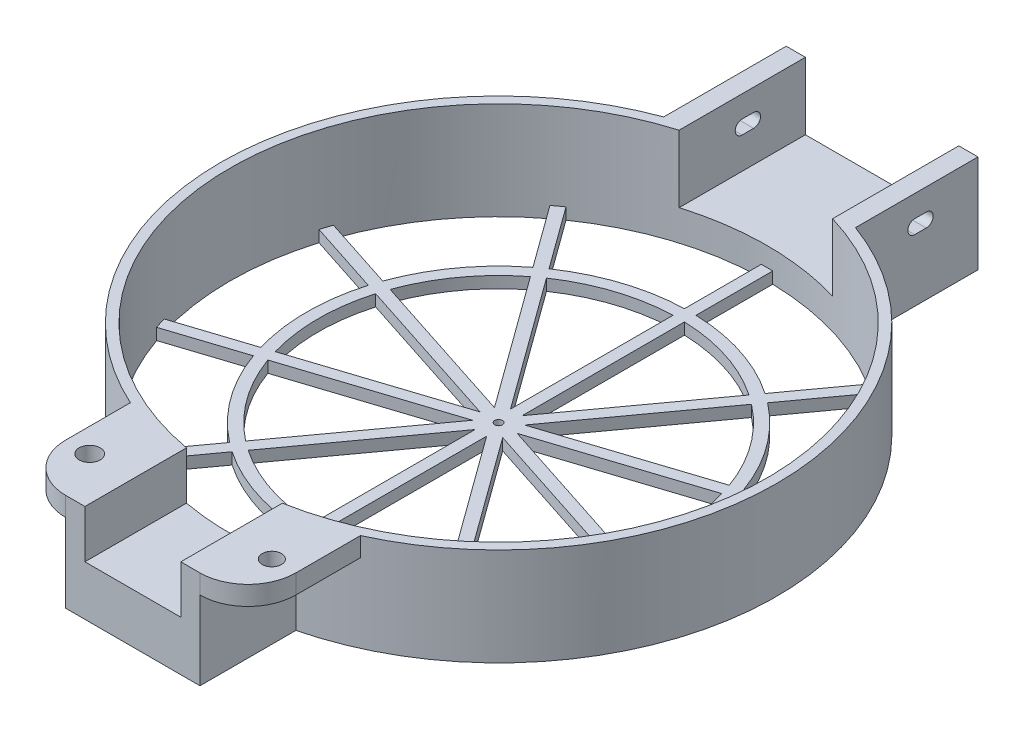
SolidWorks part; units mm, degrees
ref_plane "Front Plane" through (0, 0, 0) normal (0, 0, 1) x (1, 0, 0)
ref_plane "Top Plane" through (0, 0, 0) normal (0, 1, 0) x (1, 0, 0)
ref_plane "Right Plane" through (0, 0, 0) normal (1, 0, 0) x (0, 0, -1)
sketch "Sketch1" plane through (0, 0, 0) normal (0, 1, 0) x (1, 0, 0)
  line L0 (1.5, 69.9839) -> (0, 70.9924)
  line L2 (1.5, 69.9839) -> (1.5, 4.6165)
  line L4 (-1.5, 69.9839) -> (-1.5, 4.6165)
  line L5 (-0.8687, 69.9946) -> (-0.1565, 47.2626) construction
  line L7 (0, 70.9924) -> (-1.5, 69.9839)
  line L8 (41.7283, 57.4341) -> (39.922, 57.4999)
  line L9 (42.349, 55.7365) -> (41.7283, 57.4341)
  line L10 (42.349, 55.7365) -> (3.9271, 2.8532)
  line L11 (39.922, 57.4999) -> (1.5, 4.6165)
  line L12 (67.5178, 21.9379) -> (66.0951, 23.0528)
  line L13 (67.0222, 20.1996) -> (67.5178, 21.9379)
  line L14 (67.0222, 20.1996) -> (4.8541, 0)
  line L15 (66.0951, 23.0528) -> (3.9271, 2.8532)
  line L16 (67.5178, -21.9379) -> (67.0222, -20.1996)
  line L17 (66.0951, -23.0528) -> (67.5178, -21.9379)
  line L18 (66.0951, -23.0528) -> (3.9271, -2.8532)
  line L19 (67.0222, -20.1996) -> (4.8541, 0)
  line L20 (41.7283, -57.4341) -> (42.349, -55.7365)
  line L21 (39.922, -57.4999) -> (41.7283, -57.4341)
  line L22 (39.922, -57.4999) -> (1.5, -4.6165)
  line L23 (42.349, -55.7365) -> (3.9271, -2.8532)
  line L24 (0, -70.9924) -> (1.5, -69.9839)
  line L25 (-1.5, -69.9839) -> (0, -70.9924)
  line L26 (-1.5, -69.9839) -> (-1.5, -4.6165)
  line L27 (1.5, -69.9839) -> (1.5, -4.6165)
  line L28 (-41.7283, -57.4341) -> (-39.922, -57.4999)
  line L29 (-42.349, -55.7365) -> (-41.7283, -57.4341)
  line L30 (-42.349, -55.7365) -> (-3.9271, -2.8532)
  line L31 (-39.922, -57.4999) -> (-1.5, -4.6165)
  line L32 (-67.5178, -21.9379) -> (-66.0951, -23.0528)
  line L33 (-67.0222, -20.1996) -> (-67.5178, -21.9379)
  line L34 (-67.0222, -20.1996) -> (-4.8541, 0)
  line L35 (-66.0951, -23.0528) -> (-3.9271, -2.8532)
  line L36 (-67.5178, 21.9379) -> (-67.0222, 20.1996)
  line L37 (-66.0951, 23.0528) -> (-67.5178, 21.9379)
  line L38 (-66.0951, 23.0528) -> (-3.9271, 2.8532)
  line L39 (-67.0222, 20.1996) -> (-4.8541, 0)
  line L40 (-41.7283, 57.4341) -> (-42.349, 55.7365)
  line L41 (-39.922, 57.4999) -> (-41.7283, 57.4341)
  line L42 (-39.922, 57.4999) -> (-1.5, 4.6165)
  line L43 (-42.349, 55.7365) -> (-3.9271, 2.8532)
  line L60 (-0.1565, 47.2626) -> (0.8687, 69.9946) construction
  circle A0 centre (0, 0) radius 72.5
  circle A1 centre (0, 0) radius 70
  point P4 (0, 42.2662)
  point P59 (0, 0)
  dimension "D1" = 145
  dimension "D2" = 140
  dimension "D4" = 3
  dimension "D3" = 10
extrude "Boss-Extrude4" add sketch "Sketch1" along normal blind 16 contours A0 | A1
extrude "Boss-Extrude5" add sketch "Sketch1<11>" along normal blind 50 contours L26 L25 L24 L27 L22 L21 L20 L23 L18 L17 L16 L19 L14 L13 L12 L15 L10 L9 L8 L11 L2 L0 L7 L4 L42 L41 L40 L43 L38 L37 L36 L39 L34 L33 L32 L35 L30 L29 L28 L31
sketch "Sketch1<11>" plane through (0, 0, 0) normal (0, 1, 0) x (1, 0, 0) same geometry as "Sketch1"
sketch "Sketch2" plane through (0, 0, 0) normal (0, -1, 0) x (1, 0, 0)
  circle A0 centre (0, 0) radius 1
extrude "Cut-Extrude1" cut sketch "Sketch2" against normal through all
sketch "Sketch3" plane through (0, 0, 0) normal (0, -1, 0) x (1, 0, 0)
  circle A0 centre (0, 0) radius 47
  circle A1 centre (0, 0) radius 50
  circle A2 centre (0, 0) radius 70 construction
  dimension "D1" = 3
  dimension "D2" = 20
extrude "Boss-Extrude6" add sketch "Sketch3" against normal up to surface (50 mm away) contours A0 | A1 up to face at (0, 50, -1)
extrude "Boss-Extrude7" add sketch "Sketch1<12>" along normal blind 72.5 contours A1 | A0
sketch "Sketch1<12>" plane through (0, 0, 0) normal (0, 1, 0) x (1, 0, 0) same geometry as "Sketch1"
sketch "Sketch5" plane through (0, 0, 0) normal (0, 0, 1) x (1, 0, 0)
  line L0 (72.5, 72.5) -> (-72.5, 72.5) construction
  line L1 (-12.5, 85) -> (12.5, 85)
  line L2 (-12.5, 85) -> (-12.5, 60)
  line L3 (-12.5, 60) -> (12.5, 60)
  line L4 (12.5, 85) -> (12.5, 60)
  line L5 (-12.5, 85) -> (12.5, 60) construction
  line L6 (-12.5, 60) -> (12.5, 85) construction
  point P0 (0, 72.5)
  dimension "D1" = 25
  dimension "D2" = 25
sketch "Sketch6" plane through (0, 72.5, 0) normal (0, 1, 0) x (1, 0, 0)
  line L0 (-12.5, -1004.9467) -> (-12.5, -95.3562) construction
  line L1 (-12.5, -95.3562) -> (12.5, -95.3562)
  line L2 (12.5, -1000) -> (12.5, -95.3562) construction
  line L3 (12.5, -70.3562) -> (-12.5, -70.3562)
  line L4 (-12.5, -70.3562) -> (-12.5, 1004.2764) construction
  line L5 (12.5, -70.3562) -> (12.5, 49000) construction
  line L6 (12.5, -95.3562) -> (17.5, -95.3562)
  line L8 (12.5, -70.3562) -> (17.5, -70.3562)
  line L9 (17.5, -95.3562) -> (17.5, -70.3562)
  line L10 (-12.5, -95.3562) -> (-17.5, -95.3562)
  line L12 (-12.5, -70.3562) -> (-17.5, -70.3562)
  line L13 (-17.5, -95.3562) -> (-17.5, -70.3562)
  circle A0 centre (0, 0) radius 72.5 construction
  dimension "D1" = 5
  dimension "D2" = 5
  dimension "D3" = 25
  dimension "D4" = 25
  dimension "D5" = 12.5
extrude "Boss-Extrude8" add sketch "Sketch6" against normal blind 26
extrude "Cut-Extrude4" cut sketch "Sketch5" along normal blind 137.5
sketch "Sketch7" plane through (0, 72.5, 0) normal (0, 1, 0) x (1, 0, 0)
  line L1 (-17.5, -70.3562) -> (-17.5, -95.3562) construction
  line L2 (17.5, -95.3562) -> (17.5, -70.3562) construction
  line L6 (-30, -82.8562) -> (-30, -66.0019)
  line L7 (-30, -66.0019) -> (-17.5, -70.3562)
  line L8 (30, -82.8562) -> (30, -66.0019)
  line L9 (30, -66.0019) -> (17.5, -70.3562)
  line L10 (-17.5, -70.3562) -> (-17.5, -95.3562)
  line L11 (17.5, -70.3562) -> (17.5, -95.3562)
  line L13 (12.5, -95.3562) -> (-12.5, -95.3562) construction
  arc A0 (-30, -82.8562) -> (-17.5, -95.3562) centre (-17.5, -82.8562) ccw
  arc A1 (17.5, -95.3562) -> (30, -82.8562) centre (17.5, -82.8562) ccw
  circle A2 centre (0, 0) radius 72.5 construction
  circle A3 centre (-23.75, -82.8562) radius 2.75
  circle A4 centre (23.75, -82.8562) radius 2.5
  point P6 (0, -82.8562)
  dimension "D1" = 12.5
  dimension "D4" = 5.5
  dimension "D5" = 12.5
  dimension "D6" = 5
  dimension "D8" = 12.5
  dimension "D2" = 12.5
  dimension "D3" = 6.25
  dimension "D7" = 6.25
extrude "Boss-Extrude9" add sketch "Sketch7" against normal blind 5
sketch "Sketch12" plane through (0, 0, 0) normal (0, 0, 1) x (1, 0, 0)
  line L0 (72.5, 72.5) -> (-72.5, 72.5) construction
  line L1 (20, 95) -> (-20, 95)
  line L2 (20, 95) -> (20, 50)
  line L3 (20, 50) -> (-20, 50)
  line L4 (-20, 95) -> (-20, 50)
  line L5 (20, 95) -> (-20, 50) construction
  line L6 (20, 50) -> (-20, 95) construction
  point P0 (0, 72.5)
  dimension "D1" = 40
  dimension "D2" = 22.5
extrude "Cut-Extrude5" cut sketch "Sketch12" against normal blind 180
sketch "Sketch15" plane through (0, 72.5, 0) normal (0, 1, 0) x (1, 0, 0)
  line L0 (-20, 69.6868) -> (-20, 99.6868) construction
  line L1 (-25, 103.0533) -> (25, 103.0533)
  line L3 (20, 69.6868) -> (20, 99.6868) construction
  line L4 (25, 103.0533) -> (25, 68.0533)
  line L5 (-25, 103.0533) -> (-25, 68.0533)
  arc A0 (30, -66.0019) -> (20, 69.6868) centre (0, 0) ccw construction
  arc A1 (-20, 69.6868) -> (-30, -66.0019) centre (0, 0) ccw construction
  arc A2 (-25, 68.0533) -> (25, 68.0533) centre (0, 0) cw
  dimension "D1" = 30
  dimension "D2" = 5
  dimension "D3" = 5
  dimension "D4" = 35
  dimension "D5" = 35
extrude "Boss-Extrude11" add sketch "Sketch15" against normal blind 49.5969
extrude "Cut-Extrude6" cut sketch "Sketch12<2>" against normal blind 199.5
sketch "Sketch12<2>" plane through (0, 0, 0) normal (0, 0, 1) x (1, 0, 0) same geometry as "Sketch12"
sketch "Sketch17" plane through (0, 22.9031, 0) normal (0, -1, 0) x (1, 0, 0)
  line L3 (26.6747, -100.002) -> (-27.9148, -100.002)
  line L4 (26.6747, -100.002) -> (26.6747, -105.8478)
  line L5 (26.6747, -105.8478) -> (-27.9148, -105.8478)
  line L6 (-27.9148, -100.002) -> (-27.9148, -105.8478)
extrude "Cut-Extrude7" cut sketch "Sketch17" against normal through all both and the other way through all
sketch "Sketch20" plane through (25, 0, 0) normal (1, 0, 0) x (0, 0, -1)
  line L0 (83.502, 65) -> (86.502, 65) construction
  line L1 (83.502, 66.8) -> (86.502, 66.8)
  line L2 (83.502, 63.2) -> (86.502, 63.2)
  line L3 (100.002, 50) -> (67.082, 50) construction
  line L4 (100.002, 72.5) -> (100.002, 22.9031) construction
  arc A0 (83.502, 66.8) -> (83.502, 63.2) centre (83.502, 65) ccw
  arc A1 (86.502, 63.2) -> (86.502, 66.8) centre (86.502, 65) ccw
  point P2 (85.002, 65)
  dimension "D1" = 1.8
  dimension "D2" = 3
  dimension "D3" = 15
  dimension "D4" = 15
extrude "Cut-Extrude8" cut sketch "Sketch20" against normal through all both and the other way through all
sketch "Sketch22" plane through (0, 22.9031, 0) normal (0, -1, 0) x (1, 0, 0)
  line L1 (-5, -82.3274) -> (5, -82.3274)
  line L2 (-5, -82.3274) -> (-5, -72.3274)
  line L3 (-5, -72.3274) -> (5, -72.3274)
  line L4 (5, -82.3274) -> (5, -72.3274)
  line L5 (-5, -82.3274) -> (5, -72.3274) construction
  line L6 (-5, -72.3274) -> (5, -82.3274) construction
  circle A0 centre (0, 0) radius 72.5 construction
  point P0 (0, -77.3274)
  dimension "D1" = 10
  dimension "D2" = 10
extrude "Boss-Extrude12" add sketch "Sketch22" along normal up to surface (22.9031 mm away) up to face at (-47.5332, 0, 34.5349)
sketch "Sketch24" plane through (1.5, 0, 0) normal (1, 0, 0) x (0, 0, -1)
  line L1 (-93.1955, 47) -> (122.6721, 47)
  line L2 (-93.1955, 47) -> (-93.1955, -14.868)
  line L3 (-93.1955, -14.868) -> (122.6721, -14.868)
  line L4 (122.6721, 47) -> (122.6721, -14.868)
  line L5 (46.9761, 50) -> (4.6165, 50) construction
  dimension "D1" = 3
extrude "Cut-Extrude9" cut sketch "Sketch24" against normal through all both and the other way through all
sketch "Sketch25" plane through (0, 50, 0) normal (0, 1, 0) x (1, 0, 0)
  line L0 (20, 67.082) -> (20, 100.002) construction
  line L3 (-20, 67.082) -> (-20, 100.002)
  line L4 (-20, 100.002) -> (20, 100.002)
  line L5 (20, 67.082) -> (20, 100.002)
  arc A0 (-20, 67.082) -> (20, 67.082) centre (0, 0) cw
extrude "Boss-Extrude13" add sketch "Sketch25" along normal blind 5
sketch "Sketch27" plane through (0, 0, 93.1955) normal (0, 0, -1) x (-1, 0, 0)
  line L0 (-25, 47) -> (25, 47) construction
  line L1 (-18.5533, 47) -> (21.8192, 47)
  line L2 (-18.5533, 47) -> (-18.5533, 41.121)
  line L3 (-18.5533, 41.121) -> (21.8192, 41.121)
  line L4 (21.8192, 47) -> (21.8192, 41.121)
extrude "Cut-Extrude11" cut sketch "Sketch27" against normal blind 5
